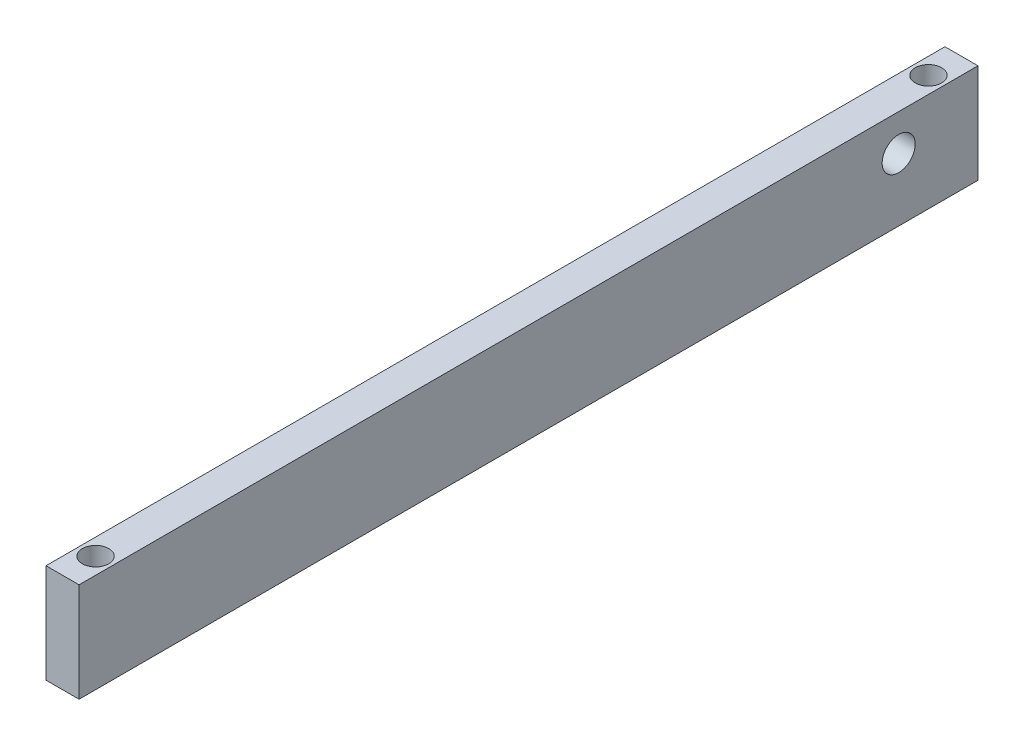
SolidWorks part; units mm, degrees
ref_plane "Front Plane" through (0, 0, 0) normal (0, 0, 1) x (1, 0, 0)
ref_plane "Top Plane" through (0, 0, 0) normal (0, 1, 0) x (1, 0, 0)
ref_plane "Right Plane" through (0, 0, 0) normal (1, 0, 0) x (0, 0, -1)
sketch "Sketch1" plane through (0, 0, 0) normal (0, 0, 1) x (1, 0, 0)
  line L0 (0, 0) -> (-12.7, 0)
  line L1 (-12.7, 0) -> (-12.7, 19.05)
  line L2 (-12.7, 19.05) -> (-6.35, 19.05)
  line L3 (-6.35, 19.05) -> (-6.35, 6.35)
  line L4 (-6.35, 6.35) -> (0, 6.35)
  line L5 (0, 6.35) -> (0, 0)
  dimension "D1" = 6.35
  dimension "D2" = 6.35
  dimension "D3" = 6.35
  dimension "D4" = 12.7
extrude "Boss-Extrude1" add sketch "Sketch1" against normal blind 172.72
sketch "Sketch2" plane through (-12.7, 0, 0) normal (-1, 0, 0) x (0, 0, 1)
  line L0 (-172.72, 0) -> (0, 0) construction
  line L1 (-172.72, 19.05) -> (-172.72, 0) construction
  circle A0 centre (-157.48, 12.065) radius 3.175
  dimension "D1" = 6.35
  dimension "D2" = 12.065
  dimension "D3" = 15.24
extrude "Cut-Extrude1" cut sketch "Sketch2" against normal up to next
sketch "Sketch3" plane through (0, 19.05, 0) normal (0, 1, 0) x (1, 0, 0)
  line L2 (-6.35, 0) -> (-12.7, 0) construction
  line L3 (-9.525, 163.83) -> (-9.525, 0) construction
  circle A0 centre (-9.525, 6.35) radius 2.54
  dimension "D1" = 5.08
  dimension "D2" = 6.35
sketch "Sketch4" plane through (0, 0, 0) normal (0, -1, 0) x (1, 0, 0)
  line L0 (-9.525, 0) -> (-9.525, -172.72) construction
  line L1 (-12.7, 0) -> (0, 0) construction
  line L2 (-12.7, -172.72) -> (0, -172.72) construction
  line L3 (0, -172.72) -> (0, 0) construction
  circle A0 centre (-9.525, -166.37) radius 2.54
  circle A1 centre (-9.525, -6.35) radius 2.54
  dimension "D2" = 5.08
  dimension "D1" = 9.525
  dimension "D3" = 6.35
  dimension "D4" = 6.35
sketch "Sketch5" plane through (0, 0, -172.72) normal (0, 0, -1) x (-1, 0, 0)
  line L1 (6.35, 6.35) -> (0, 6.35)
  line L2 (6.35, 6.35) -> (6.35, 0)
  line L3 (6.35, 0) -> (0, 0)
  line L4 (0, 6.35) -> (0, 0)
extrude "Cut-Extrude4" cut sketch "Sketch5" against normal blind 345.44
extrude "Cut-Extrude5" cut sketch "Sketch3" against normal through all
extrude "Cut-Extrude6" cut sketch "Sketch4" against normal through all
